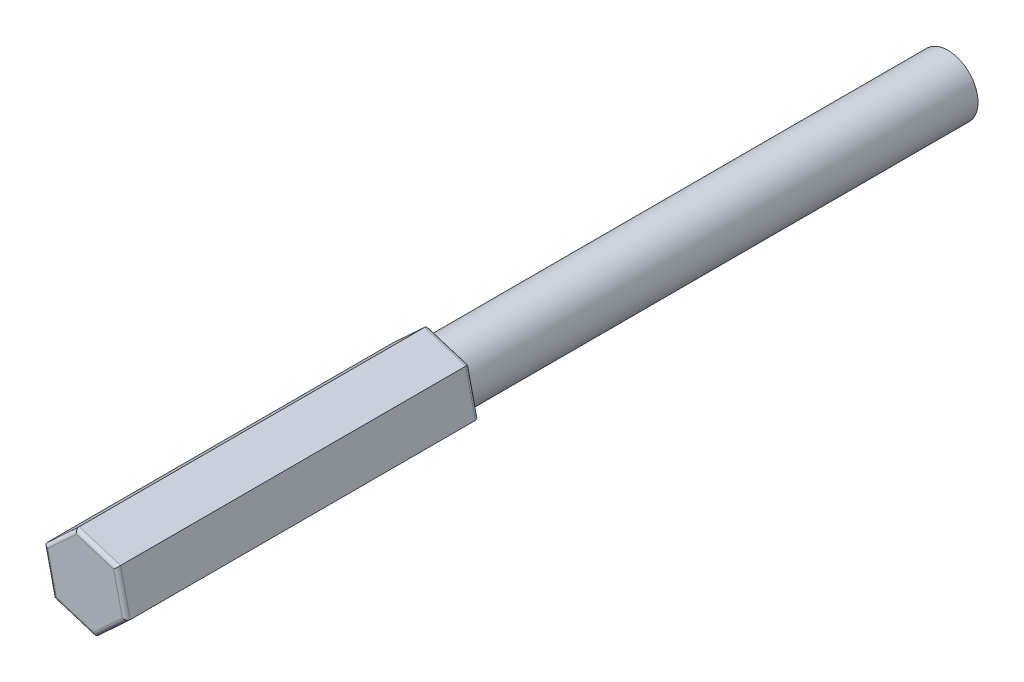
SolidWorks part; units mm, degrees
ref_plane "Front Plane" through (0, 0, 0) normal (0, 0, 1) x (1, 0, 0)
ref_plane "Top Plane" through (0, 0, 0) normal (0, 1, 0) x (1, 0, 0)
ref_plane "Right Plane" through (0, 0, 0) normal (1, 0, 0) x (0, 0, -1)
sketch "Sketch1" plane through (0, 0, 0) normal (0, 0, 1) x (1, 0, 0)
  circle A0 centre (0, 0) radius 4
  dimension "D1" = 8
extrude "Boss-Extrude1" add sketch "Sketch1" along normal blind 85 and the other way blind 30
sketch "Sketch2" plane through (0, 0, 85) normal (0, 0, 1) x (1, 0, 0)
  line L1 (5.5133, -1.7136) -> (4.2407, 3.9179)
  line L2 (4.2407, 3.9179) -> (-1.2726, 5.6315)
  line L3 (-1.2726, 5.6315) -> (-5.5133, 1.7136)
  line L4 (-5.5133, 1.7136) -> (-4.2407, -3.9179)
  line L5 (-4.2407, -3.9179) -> (1.2726, -5.6315)
  line L6 (1.2726, -5.6315) -> (5.5133, -1.7136)
  circle A0 centre (0, 0) radius 5 construction
  dimension "D1" = 10
extrude "Boss-Extrude2" add sketch "Sketch2" against normal blind 47
fillet "Fillet1" radius 0.5 13 edges at (-1.484, -4.7747, 85) (-4.877, -1.1021, 85) (-3.393, 3.6726, 85) (1.484, 4.7747, 85) (4.877, 1.1021, 85) (3.393, -3.6726, 85) (4.877, 1.1021, 38) (1.484, 4.7747, 38) (-3.393, 3.6726, 38) (-4.877, -1.1021, 38) (-1.484, -4.7747, 38) (3.393, -3.6726, 38) (4, 0, 38)
